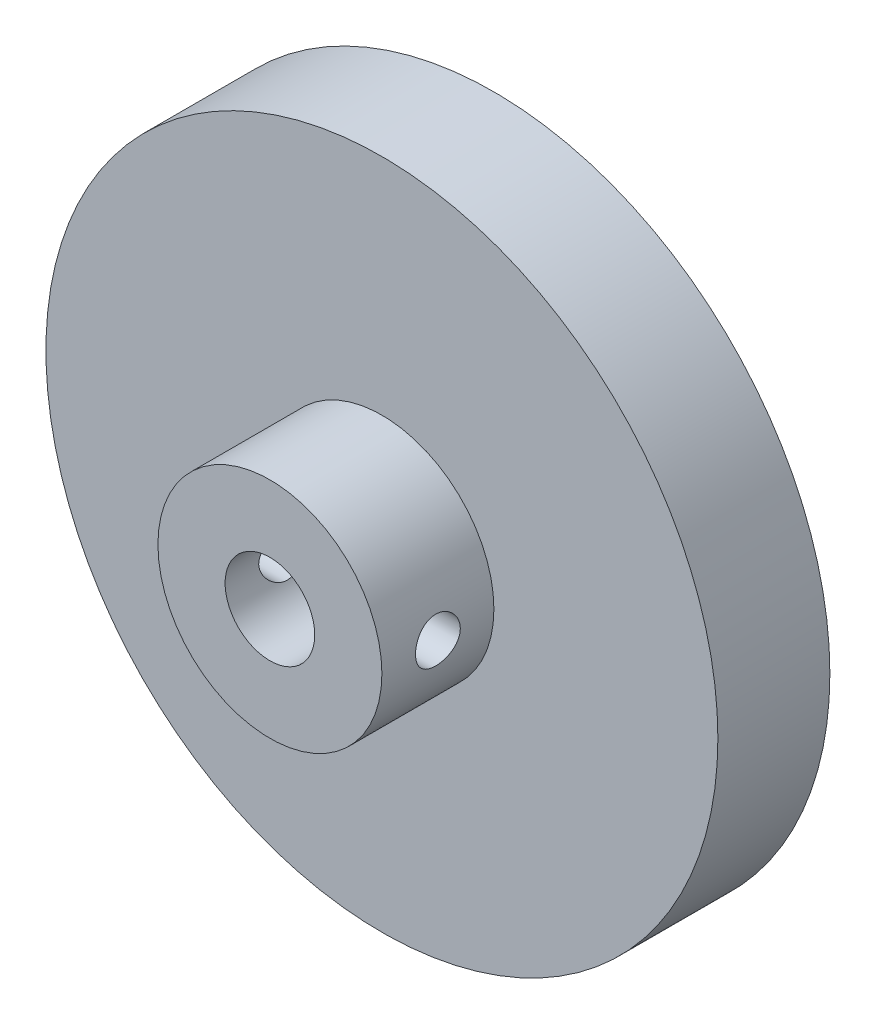
SolidWorks part; units mm, degrees
ref_plane "Front Plane" through (0, 0, 0) normal (0, 0, 1) x (1, 0, 0)
ref_plane "Top Plane" through (0, 0, 0) normal (0, 1, 0) x (1, 0, 0)
ref_plane "Right Plane" through (0, 0, 0) normal (1, 0, 0) x (0, 0, -1)
sketch "Sketch1" plane through (0, 0, 0) normal (0, 0, 1) x (1, 0, 0)
  circle A0 centre (0, 0) radius 30
  dimension "D1" = 60
extrude "Boss-Extrude1" add sketch "Sketch1" along normal blind 10
sketch "Sketch2" plane through (0, 0, 10) normal (0, 0, 1) x (1, 0, 0)
  circle A0 centre (0, 0) radius 10
  circle A1 centre (0, 0) radius 4
extrude "Boss-Extrude2" add sketch "Sketch2" along normal blind 10
sketch "Sketch3" plane through (0, 0, 0) normal (1, 0, 0) x (0, 0, -1)
  line L0 (-20, 10) -> (-20, -10) construction
  line L1 (-10, 10) -> (-20, 10) construction
  circle A0 centre (-15, 0) radius 2
  dimension "D1" = 5
  dimension "D2" = 10
extrude "Cut-Extrude1" cut sketch "Sketch3" against normal blind 10 and the other way blind 10
